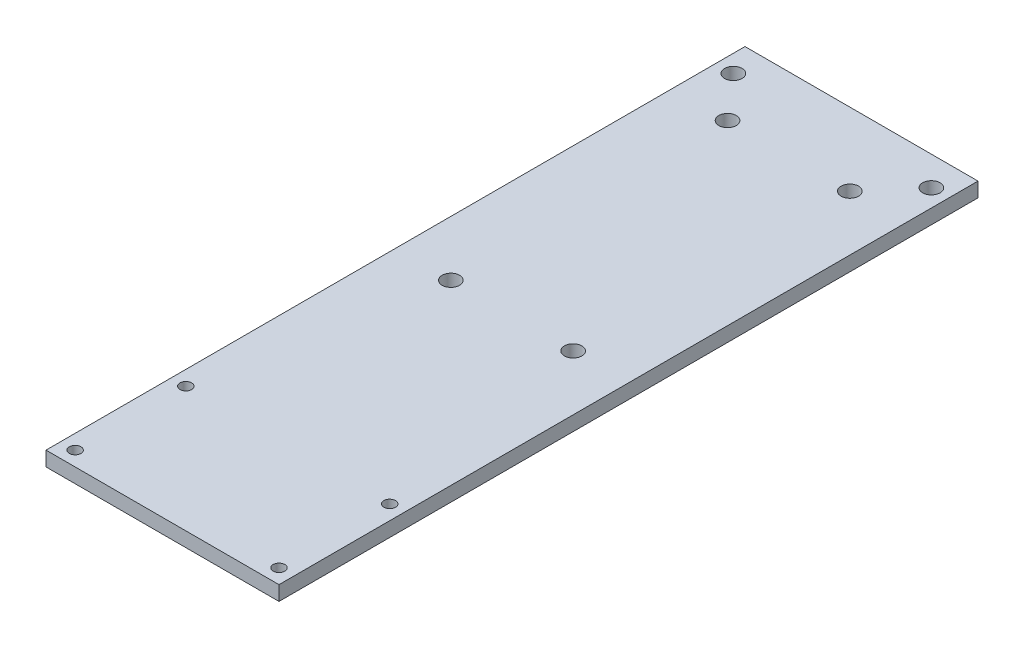
SolidWorks part; units mm, degrees
material "6061-T6 (SS)"
ref_plane "Front Plane" through (0, 0, 0) normal (0, 0, 1) x (1, 0, 0)
ref_plane "Top Plane" through (0, 0, 0) normal (0, 1, 0) x (1, 0, 0)
ref_plane "Right Plane" through (0, 0, 0) normal (1, 0, 0) x (0, 0, -1)
sketch "Plate sketch" plane through (0, 0, 0) normal (0, 1, 0) x (1, 0, 0)
  line L1 (-40, -120) -> (40, -120)
  line L2 (-40, -120) -> (-40, 120)
  line L3 (-40, 120) -> (40, 120)
  line L4 (40, -120) -> (40, 120)
  line L5 (-40, -120) -> (40, 120) construction
  line L6 (-40, 120) -> (40, -120) construction
  point P0 (0, 0)
  dimension "D1" = 240
  dimension "D2" = 80
extrude "Plate extrude" add sketch "Plate sketch" along normal blind 5
hole_wizard "Ø6.0mm Dowel Hole2" positions "Sketch4" profile "Sketch5" hole size "Ø6.0" standard "ANSI Metric" end condition through all
sketch "Sketch4" plane through (0, 5, 0) normal (0, 1, 0) x (1, 0, 0)
  line L17 (-21, 95) -> (21, 95) construction
  line L18 (-21, 95) -> (-21, 0) construction
  line L19 (-21, 0) -> (21, 0) construction
  line L20 (21, 95) -> (21, 0) construction
  line L21 (40, 120) -> (-40, 120) construction
  line L27 (-40, 120) -> (-40, -120) construction
  point P155 (-21, 95)
  point P156 (21, 0)
  point P159 (-21, 0)
  point P160 (21, 95)
  dimension "D1" = 42
  dimension "D2" = 95
  dimension "D3" = 25
  dimension "D4" = 19
sketch "Sketch5" plane through (-21, 5, -95) normal (1, 0, 0) x (0, 0, 1)
  line L0 (0, 0) -> (0, 5)
  line L1 (0, 5) -> (3, 5)
  line L2 (3, 5) -> (3, 0)
  line L5 (3, 0) -> (0, 0)
  line L11 (0, -6.35) -> (0, 107.95) construction
  dimension "Thru Hole Dia." = 6
  dimension "Thru Hole Depth" = 5
hole_wizard "Ø4.0mm Dowel Hole1" positions "Sketch7" profile "Sketch8" hole size "Ø4.0" standard "ANSI Metric" end condition through all
sketch "Sketch7" plane through (0, 5, 0) normal (0, 1, 0) x (1, 0, 0)
  line L4 (-40, -120) -> (-30, -120) construction
  line L5 (-40, -120) -> (-40, -72) construction
  line L6 (-40, -72) -> (-30, -72) construction
  line L7 (-30, -120) -> (-30, -72) construction
  line L13 (0, -1000) -> (0, 49000) construction
  line L14 (30, -120) -> (30, -72) construction
  line L15 (40, -72) -> (30, -72) construction
  line L16 (40, -120) -> (40, -72) construction
  line L17 (40, -120) -> (30, -120) construction
  point P164 (-35, -77)
  point P166 (-35, -115)
  point P174 (-35, -72)
  point P195 (35, -115)
  point P196 (35, -77)
  dimension "D4" = 48
  dimension "D5" = 10
  dimension "D6" = 5
  dimension "D7" = 5
  dimension "D8" = 5
sketch "Sketch8" plane through (35, 5, 77) normal (1, 0, 0) x (0, 0, 1)
  line L0 (0, 0) -> (0, 5)
  line L1 (0, 5) -> (2, 5)
  line L2 (2, 5) -> (2, 0)
  line L5 (2, 0) -> (0, 0)
  line L11 (0, -6.35) -> (0, 107.95) construction
  dimension "Thru Hole Dia." = 4
  dimension "Thru Hole Depth" = 5
hole_wizard "Ø6.0mm Dowel Hole1" positions "Sketch9" profile "Sketch10" hole size "Ø6.0" standard "ANSI Metric" end condition through all
sketch "Sketch9" plane through (0, 5, 0) normal (0, 1, 0) x (1, 0, 0)
  line L0 (40, 120) -> (-40, 120) construction
  line L3 (40, -120) -> (40, 120) construction
  line L4 (-40, 120) -> (-40, -120) construction
  point P0 (-34, 110)
  point P2 (34, 110)
  dimension "D1" = 10
  dimension "D2" = 10
  dimension "D3" = 6
  dimension "D4" = 6
sketch "Sketch10" plane through (-34, 5, -110) normal (1, 0, 0) x (0, 0, 1)
  line L0 (0, 0) -> (0, 5)
  line L1 (0, 5) -> (3, 5)
  line L2 (3, 5) -> (3, 0)
  line L5 (3, 0) -> (0, 0)
  line L11 (0, -6.35) -> (0, 107.95) construction
  dimension "Thru Hole Dia." = 6
  dimension "Thru Hole Depth" = 5
